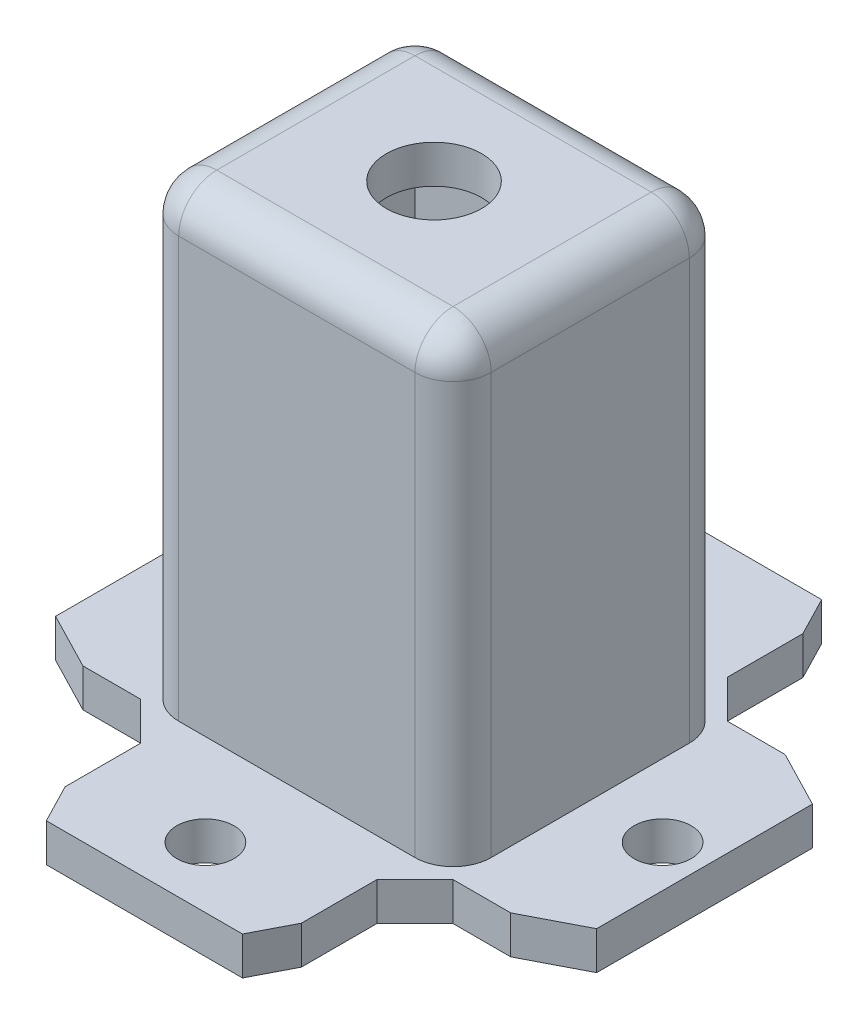
SolidWorks part; units mm, degrees
ref_plane "Front Plane" through (0, 0, 0) normal (0, 0, 1) x (1, 0, 0)
ref_plane "Top Plane" through (0, 0, 0) normal (0, 1, 0) x (1, 0, 0)
ref_plane "Right Plane" through (0, 0, 0) normal (1, 0, 0) x (0, 0, -1)
sketch "Sketch3" plane through (-6, 0, 0) normal (-1, 0, 0) x (0, 0, 1)
  line L2 (5.2, 81) -> (5.2, 105.05)
  line L3 (15.2, 83) -> (15.2, 81)
  line L4 (5, 96) -> (5, 82) construction
  line L5 (7.2, 83) -> (7.2, 85.3787)
  line L6 (-15.2, 81) -> (-5.2, 81)
  line L7 (7.2, 83) -> (15.2, 83)
  line L8 (10.6023, 81) -> (7.5227, 81) construction
  line L10 (10.6023, 81) -> (16.4534, 81) construction
  line L12 (4.5, 81) -> (7.5227, 81) construction
  line L13 (5.2, 83) -> (5.2, 85.3787) construction
  line L15 (-7.2, 107.05) -> (7.2, 107.05)
  line L16 (7.2, 85.3787) -> (7.2, 107.05)
  line L17 (-15.2, 83) -> (-15.2, 81)
  line L18 (0, 78) -> (0, 92.4336) construction
  line L19 (4.5, 78) -> (-4.5, 78) construction
  line L21 (-7.2, 83) -> (-15.2, 83)
  line L23 (-5.2, 81) -> (-5.2, 105.05)
  line L24 (-7.2, 83) -> (-7.2, 107.05)
  line L25 (-16.4534, 81) -> (-10.6023, 81) construction
  line L26 (5.2, 81) -> (15.2, 81)
  line L27 (-5.2, 105.05) -> (5.2, 105.05)
  dimension "D1" = 0.2
  dimension "D2" = 2
  dimension "D3" = 2
  dimension "D4" = 2
  dimension "D6" = 8
extrude "Boss-Extrude1" add sketch "Sketch3" against normal blind 12.4 from offset 0.2
sketch "Sketch4" plane through (0, 107.05, 0) normal (0, 1, 0) x (1, 0, 0)
  circle A0 centre (0, 0) radius 2.5
  dimension "D1" = 5
extrude "Cut-Extrude1" cut sketch "Sketch4" against normal blind 12
sketch "Sketch5" plane through (0, 83, 0) normal (0, 1, 0) x (1, 0, 0)
  circle A0 centre (0, 12) radius 1.5
  circle A1 centre (0, -12) radius 1.5
  dimension "D1" = 3
  dimension "D2" = 3
  dimension "D3" = 12
  dimension "D4" = 12
extrude "Cut-Extrude2" cut sketch "Sketch5" against normal blind 12
sketch "Sketch7" plane through (0, 0, -7.2) normal (0, 0, -1) x (-1, 0, 0)
  line L1 (14.2, 83) -> (14.2, 81)
  line L2 (10.6023, 81) -> (16.4534, 81) construction
  line L4 (0, 107.05) -> (0, 93.5262) construction
  line L5 (14.2, 83) -> (8.2, 83)
  line L6 (8.2, 83) -> (8.2, 107.05)
  line L8 (-6.2, 107.05) -> (6.2, 107.05) construction
  line L9 (6.2, 107.05) -> (6.2, 81)
  line L10 (-8.2, 107.05) -> (-6.2, 107.05)
  line L11 (-6.2, 81) -> (-14.2, 81)
  line L12 (6.2, 81) -> (14.2, 81)
  line L13 (8.2, 107.05) -> (6.2, 107.05)
  line L14 (-6.2, 107.05) -> (-6.2, 81)
  line L15 (-8.2, 83) -> (-8.2, 107.05)
  line L16 (-14.2, 83) -> (-8.2, 83)
  line L17 (-14.2, 83) -> (-14.2, 81)
  dimension "D1" = 8
  dimension "D2" = 2
  dimension "D3" = 2
extrude "Boss-Extrude3" add sketch "Sketch7" against normal up to surface (14.4 mm away) up to face at (0, 95.025, 7.2)
pattern_circular "CirPattern1" count 2 over 90 about axis through (0, 107.05, 0) along (0, 1, 0) of "Cut-Extrude2"
sketch "Sketch11" plane through (0, 83, 0) normal (0, 1, 0) x (1, 0, 0)
  line L4 (16.4534, 4.5) -> (10.6023, 7.5227) construction
  line L5 (-10.6023, 7.5227) -> (-16.4534, 4.5) construction
  line L6 (7.5227, 10.6023) -> (4.5, 16.4534) construction
  line L7 (-4.5, 16.4534) -> (-7.5227, 10.6023) construction
  line L8 (16.4534, 4.5) -> (10.6023, 7.5227)
  line L9 (-10.6023, 7.5227) -> (-16.4534, 4.5)
  line L10 (7.5227, 10.6023) -> (4.5, 16.4534)
  line L11 (-4.5, 16.4534) -> (-7.5227, 10.6023)
  line L12 (-4.5, 16.4534) -> (4.5, 16.4534)
  line L13 (0, 0) -> (6.1652, 0) construction
  line L14 (-4.5, -16.4534) -> (4.5, -16.4534)
  line L15 (-4.5, -16.4534) -> (-7.5227, -10.6023)
  line L16 (7.5227, -10.6023) -> (4.5, -16.4534)
  line L17 (-10.6023, -7.5227) -> (-16.4534, -4.5)
  line L18 (16.4534, -4.5) -> (10.6023, -7.5227)
  line L19 (-16.4534, 4.5) -> (-16.4534, -4.5)
  line L20 (16.4534, 4.5) -> (16.4534, -4.5)
  line L21 (18.4534, 5.7179) -> (11.9358, 9.0849)
  line L22 (9.0849, 11.9358) -> (5.7179, 18.4534)
  line L23 (-5.7179, 18.4534) -> (5.7179, 18.4534)
  line L24 (-5.7179, 18.4534) -> (-9.0849, 11.9358)
  line L25 (-11.9358, 9.0849) -> (-18.4534, 5.7179)
  line L26 (-18.4534, 5.7179) -> (-18.4534, -5.7179)
  line L27 (-11.9358, -9.0849) -> (-18.4534, -5.7179)
  line L28 (-5.7179, -18.4534) -> (-9.0849, -11.9358)
  line L29 (-5.7179, -18.4534) -> (5.7179, -18.4534)
  line L30 (9.0849, -11.9358) -> (5.7179, -18.4534)
  line L31 (18.4534, -5.7179) -> (11.9358, -9.0849)
  line L32 (18.4534, 5.7179) -> (18.4534, -5.7179)
  arc A0 (10.6023, 7.5227) -> (7.5227, 10.6023) centre (0, 0) ccw construction
  arc A1 (-7.5227, 10.6023) -> (-10.6023, 7.5227) centre (0, 0) ccw construction
  arc A2 (10.6023, 7.5227) -> (7.5227, 10.6023) centre (0, 0) ccw
  arc A3 (-7.5227, 10.6023) -> (-10.6023, 7.5227) centre (0, 0) ccw
  arc A4 (-7.5227, -10.6023) -> (-10.6023, -7.5227) centre (0, 0) cw
  arc A5 (10.6023, -7.5227) -> (7.5227, -10.6023) centre (0, 0) cw
  arc A6 (11.9358, 9.0849) -> (9.0849, 11.9358) centre (0, 0) ccw
  arc A7 (-9.0849, 11.9358) -> (-11.9358, 9.0849) centre (0, 0) ccw
  arc A8 (-9.0849, -11.9358) -> (-11.9358, -9.0849) centre (0, 0) cw
  arc A9 (11.9358, -9.0849) -> (9.0849, -11.9358) centre (0, 0) cw
  dimension "D1" = 2
extrude "Cut-Extrude3" cut sketch "Sketch11" against normal blind 10
chamfer "Chamfer1" distance 2 angle 45 3 edges at (6.2, 82, -7.2) (6.2, 82, 7.2) (-6.2, 82, 7.2)
fillet "Fillet1" radius 2 8 edges at (-8.2, 95.025, -7.2) (8.2, 95.025, -7.2) (8.2, 95.025, 7.2) (-8.2, 95.025, 7.2) (0, 107.05, -7.2) (-8.2, 107.05, 0) (0, 107.05, 7.2) (8.2, 107.05, 0)
